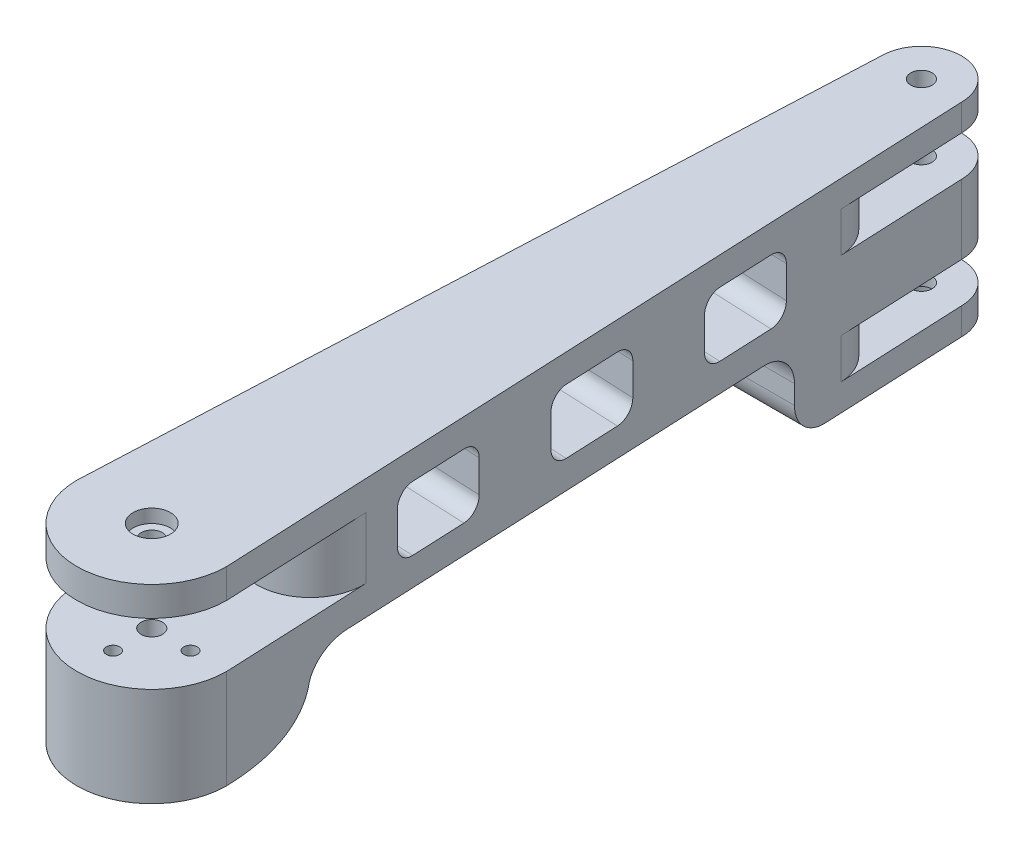
SolidWorks part; units mm, degrees
ref_plane "Ön Düzlem" through (0, 0, 0) normal (0, 0, 1) x (1, 0, 0)
ref_plane "Üst Düzlem" through (0, 0, 0) normal (0, 1, 0) x (1, 0, 0)
ref_plane "Sağ Düzlem" through (0, 0, 0) normal (1, 0, 0) x (0, 0, -1)
sketch "Sketch1" plane through (0, 0, 0) normal (0, 1, 0) x (1, 0, 0)
  line L0 (7.5, 144) -> (14, 0)
  line L1 (0, 144) -> (0, 82.4191) construction
  line L2 (-7.5, 144) -> (-14, 0)
  circle A0 centre (0, 0) radius 14
  circle A1 centre (0, 144) radius 7.5
  dimension "D1" = 28
  dimension "D2" = 15
  dimension "D3" = 144
extrude "Boss-Extrude1" add sketch "Sketch1" along normal blind 36 contours A1 L2 A0 L0 | L0 A0 L2 | A1 region at (0, 0, -144) region at (0, 0, -68.9596) region at (0, 0, 0)
sketch "Sketch2" plane through (0, 36, 0) normal (0, 1, 0) x (1, 0, 0)
  circle A0 centre (0, 0) radius 17
extrude "Cut-Extrude1" cut sketch "Sketch2" against normal blind 11.5 from offset 5.5 offset against normal yes
fillet "Fillet1" radius 10 2 edges at (13.5357, 24.75, -10.2851) (-13.5357, 24.75, -10.2851)
sketch "Sketch3" plane through (0, 0, 0) normal (0, -1, 0) x (1, 0, 0)
  circle A0 centre (0, 0) radius 11
extrude "Cut-Extrude2" cut sketch "Sketch3" against normal blind 5.6
sketch "Sketch4" plane through (0, 5.6, 0) normal (0, -1, 0) x (1, 0, 0)
  circle A0 centre (0, -7.25) radius 1.25
  circle A1 centre (-7.25, 0) radius 1.25
  circle A2 centre (0, 7.25) radius 1.25
  circle A3 centre (7.25, 0) radius 1.25
  dimension "D1" = 2.5
  dimension "D2" = 7.25
  dimension "D3" = 4
extrude "Cut-Extrude3" cut sketch "Sketch4" against normal up to surface (13.4 mm away) up to face at (0, 19, -11.5792)
sketch "Sketch5" plane through (0, 5.6, 0) normal (0, -1, 0) x (1, 0, 0)
  circle A0 centre (0, 0) radius 2
extrude "Cut-Extrude4" cut sketch "Sketch5" against normal through all
sketch "Sketch6" plane through (0, 36, 0) normal (0, 1, 0) x (1, 0, 0)
  circle A0 centre (0, 0) radius 2 construction
  circle A1 centre (0, 0) radius 2
  circle A2 centre (0, 0) radius 3.5
extrude "Cut-Extrude5" cut sketch "Sketch6" against normal blind 2.5
sketch "Sketch7" plane through (0, 36, 0) normal (0, 1, 0) x (1, 0, 0)
  line L0 (-8.1771, 129) -> (8.1771, 129)
  line L2 (14, 0) -> (7.5, 144)
  line L3 (-7.5, 144) -> (-14, 0)
  line L4 (8.1771, 129) -> (7.5, 144)
  line L5 (-7.5, 144) -> (-8.1771, 129)
  arc A2 (7.5, 144) -> (-7.5, 144) centre (0, 144) ccw
  arc A3 (-14, 0) -> (14, 0) centre (0, 0) ccw
  arc A4 (7.5, 144) -> (-7.5, 144) centre (0, 144) ccw
  arc A5 (-14, 0) -> (14, 0) centre (0, 0) ccw
  line M7 (14, 0) -> (7.5, 144)
  arc M8 (7.5, 144) -> (-7.5, 144) centre (0, 144) ccw
  line M9 (-7.5, 144) -> (-14, 0)
  dimension "D2" = 15
  dimension "D1" = 0
extrude "Cut-Extrude6" cut sketch "Sketch7" against normal blind 7.5 from offset 5 contours L0 M9 M7 M8 region at (0, 36, -139.3393) offset against normal yes
pattern_linear "LPattern1" count 2 spacing 20.5 along (0, -1, 0) of "Cut-Extrude6"
sketch "Sketch8" plane through (0, 0, 0) normal (0, -1, 0) x (1, 0, 0)
  circle A0 centre (0, -144) radius 2
extrude "Cut-Extrude7" cut sketch "Sketch8" against normal through all
fillet "Fillet2" radius 9 4 edges at (-8.1771, 27.25, -129) (-8.1771, 6.75, -129) (8.1771, 27.25, -129) (8.1771, 6.75, -129)
sketch "Sketch9" plane through (0, 0, 0) normal (0, -1, 0) x (1, 0, 0)
  line L0 (8.9776, -111.2663) -> (-8.9776, -111.2663)
  line L2 (7.5, -144) -> (14, 0)
  line L3 (-14, 0) -> (-7.5, -144)
  line L4 (8.9776, -111.2663) -> (13.2651, -16.2799)
  line L5 (-13.2651, -16.2799) -> (-8.9776, -111.2663)
  arc A0 (-13.2651, -16.2799) -> (13.2651, -16.2799) centre (0, 0) ccw
  arc A2 (14, 0) -> (-14, 0) centre (0, 0) ccw
  arc A3 (-7.5, -144) -> (7.5, -144) centre (0, -144) ccw
  dimension "D2" = 42
  dimension "D1" = 0
extrude "Cut-Extrude8" cut sketch "Sketch9" against normal blind 13.5
sketch "Sketch10" plane through (0, 0, 0) normal (0, -1, 0) x (1, 0, 0)
  line L3 (7.5, -144) -> (8.9776, -111.2663)
  line L4 (8.9776, -111.2663) -> (-8.9776, -111.2663)
  line L5 (-8.9776, -111.2663) -> (-7.5, -144)
  line L6 (7.5, -144) -> (8.9776, -111.2663)
  line L7 (8.9776, -111.2663) -> (-8.9776, -111.2663)
  line L8 (-8.9776, -111.2663) -> (-7.5, -144)
  arc A1 (-7.5, -144) -> (7.5, -144) centre (0, -144) ccw
  arc A2 (-7.5, -144) -> (7.5, -144) centre (0, -144) ccw
  dimension "D1" = 0
extrude "Boss-Extrude2" add sketch "Sketch10" along normal blind 2.0393
sketch "Sketch15" plane through (0, 36, 0) normal (0, 1, 0) x (1, 0, 0)
  circle A0 centre (0, 144) radius 2
extrude "Cut-Extrude9" cut sketch "Sketch15" against normal through all
sketch "Sketch17" plane through (0, -2.0393, 0) normal (0, -1, 0) x (1, 0, 0)
  circle A0 centre (0, -144) radius 2 construction
  circle A1 centre (0, -144) radius 2
  circle A2 centre (0, -144) radius 3.5
extrude "Cut-Extrude10" cut sketch "Sketch17" against normal blind 3
fillet "Fillet3" radius 10 1 edges at (0, 0, -21)
fillet "Fillet4" radius 6 3 edges at (0, 13.5, -21) (0, 13.5, -111.2663) (0, -2.0393, -111.2663)
sketch "Sketch18" plane through (-13.9715, 0, -0.6307) normal (-0.999, 0, -0.0451) x (-0.0451, 0, 0.999)
  line L0 (-26.7042, 24.75) -> (-121.4272, 24.75) construction
  line L1 (-26.7042, 19) -> (-26.7042, 30.5) construction
  line L2 (-79.9836, 21.75) -> (-79.9836, 27.75)
  line L3 (-106.9836, 18.75) -> (-96.9836, 18.75)
  line L4 (-109.9836, 21.75) -> (-109.9836, 27.75)
  line L5 (-106.9836, 30.75) -> (-96.9836, 30.75)
  line L6 (-93.9836, 21.75) -> (-93.9836, 27.75)
  line L7 (-109.9836, 18.75) -> (-93.9836, 30.75) construction
  line L8 (-109.9836, 30.75) -> (-93.9836, 18.75) construction
  line L9 (-76.9836, 30.75) -> (-66.9836, 30.75)
  line L10 (-63.9836, 21.75) -> (-63.9836, 27.75)
  line L11 (-76.9836, 18.75) -> (-66.9836, 18.75)
  line L12 (-49.9836, 21.75) -> (-49.9836, 27.75)
  line L13 (-46.9836, 30.75) -> (-36.9836, 30.75)
  line L14 (-33.9836, 21.75) -> (-33.9836, 27.75)
  line L15 (-46.9836, 18.75) -> (-36.9836, 18.75)
  arc A0 (-96.9836, 18.75) -> (-93.9836, 21.75) centre (-96.9836, 21.75) ccw
  arc A1 (-96.9836, 30.75) -> (-93.9836, 27.75) centre (-96.9836, 27.75) cw
  arc A2 (-109.9836, 27.75) -> (-106.9836, 30.75) centre (-106.9836, 27.75) cw
  arc A3 (-106.9836, 18.75) -> (-109.9836, 21.75) centre (-106.9836, 21.75) cw
  arc A4 (-76.9836, 18.75) -> (-79.9836, 21.75) centre (-76.9836, 21.75) cw
  arc A5 (-79.9836, 27.75) -> (-76.9836, 30.75) centre (-76.9836, 27.75) cw
  arc A6 (-66.9836, 30.75) -> (-63.9836, 27.75) centre (-66.9836, 27.75) cw
  arc A7 (-66.9836, 18.75) -> (-63.9836, 21.75) centre (-66.9836, 21.75) ccw
  arc A8 (-46.9836, 18.75) -> (-49.9836, 21.75) centre (-46.9836, 21.75) cw
  arc A9 (-49.9836, 27.75) -> (-46.9836, 30.75) centre (-46.9836, 27.75) cw
  arc A10 (-36.9836, 30.75) -> (-33.9836, 27.75) centre (-36.9836, 27.75) cw
  arc A11 (-36.9836, 18.75) -> (-33.9836, 21.75) centre (-36.9836, 21.75) ccw
  point P4 (-101.9836, 24.75)
  dimension "D3" = 3
  dimension "D1" = 16
  dimension "D2" = 12
  dimension "D4" = 3
extrude "Cut-Extrude11" cut sketch "Sketch18" against normal through all
